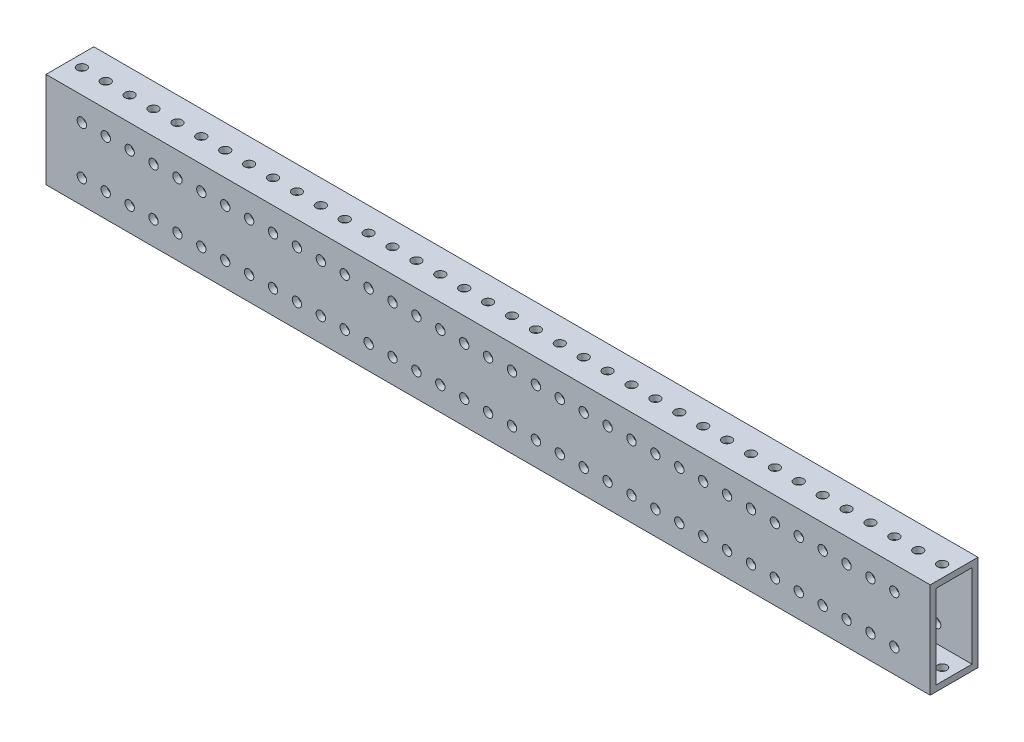
SolidWorks part; units mm, degrees
material "6061-T6 (SS)"
ref_plane "Front Plane" through (0, 0, 0) normal (0, 0, 1) x (1, 0, 0)
ref_plane "Top Plane" through (0, 0, 0) normal (0, 1, 0) x (1, 0, 0)
ref_plane "Right Plane" through (0, 0, 0) normal (1, 0, 0) x (0, 0, -1)
sketch "Sketch1" plane through (0, 0, 0) normal (0, 0, 1) x (1, 0, 0)
  line L1 (0, 0) -> (469.9, 0)
  line L2 (0, 0) -> (0, 50.8)
  line L3 (0, 50.8) -> (469.9, 50.8)
  line L4 (469.9, 0) -> (469.9, 50.8)
  dimension "D1" = 50.8
  dimension "D2" = 469.9
extrude "Boss-Extrude1" add sketch "Sketch1" along normal blind 25.4
shell "Shell1" thickness 3.175 removed face at (469.9, 25.4, 12.7) removed face at (0, 25.4, 12.7)
sketch "Sketch2" plane through (0, 0, 0) normal (0, 0, -1) x (-1, 0, 0)
  line L0 (-469.9, 50.8) -> (0, 50.8) construction
  line L1 (-469.9, 0) -> (-469.9, 50.8) construction
  circle A0 centre (-450.85, 38.1) radius 2.4892
  circle A1 centre (-438.15, 38.1) radius 2.4892
  circle A2 centre (-425.45, 38.1) radius 2.4892
  circle A3 centre (-412.75, 38.1) radius 2.4892
  circle A4 centre (-400.05, 38.1) radius 2.4892
  circle A5 centre (-387.35, 38.1) radius 2.4892
  circle A6 centre (-374.65, 38.1) radius 2.4892
  circle A7 centre (-361.95, 38.1) radius 2.4892
  circle A8 centre (-349.25, 38.1) radius 2.4892
  circle A9 centre (-336.55, 38.1) radius 2.4892
  circle A10 centre (-323.85, 38.1) radius 2.4892
  circle A11 centre (-311.15, 38.1) radius 2.4892
  circle A12 centre (-298.45, 38.1) radius 2.4892
  circle A13 centre (-285.75, 38.1) radius 2.4892
  circle A14 centre (-273.05, 38.1) radius 2.4892
  circle A15 centre (-260.35, 38.1) radius 2.4892
  circle A16 centre (-247.65, 38.1) radius 2.4892
  circle A17 centre (-234.95, 38.1) radius 2.4892
  circle A18 centre (-222.25, 38.1) radius 2.4892
  circle A19 centre (-209.55, 38.1) radius 2.4892
  circle A20 centre (-196.85, 38.1) radius 2.4892
  circle A21 centre (-184.15, 38.1) radius 2.4892
  circle A22 centre (-171.45, 38.1) radius 2.4892
  circle A23 centre (-158.75, 38.1) radius 2.4892
  circle A24 centre (-146.05, 38.1) radius 2.4892
  circle A25 centre (-133.35, 38.1) radius 2.4892
  circle A26 centre (-120.65, 38.1) radius 2.4892
  circle A27 centre (-107.95, 38.1) radius 2.4892
  circle A28 centre (-95.25, 38.1) radius 2.4892
  circle A29 centre (-82.55, 38.1) radius 2.4892
  circle A30 centre (-69.85, 38.1) radius 2.4892
  circle A31 centre (-57.15, 38.1) radius 2.4892
  circle A32 centre (-44.45, 38.1) radius 2.4892
  circle A33 centre (-31.75, 38.1) radius 2.4892
  circle A34 centre (-19.05, 38.1) radius 2.4892
  circle A35 centre (-6.35, 38.1) radius 2.4892 construction
  circle A36 centre (6.35, 38.1) radius 2.4892 construction
  circle A37 centre (19.05, 38.1) radius 2.4892 construction
  circle A38 centre (31.75, 38.1) radius 2.4892 construction
  circle A39 centre (44.45, 38.1) radius 2.4892 construction
  circle A40 centre (-438.15, 12.7) radius 2.4892
  circle A41 centre (-425.45, 12.7) radius 2.4892
  circle A42 centre (-412.75, 12.7) radius 2.4892
  circle A43 centre (-400.05, 12.7) radius 2.4892
  circle A44 centre (-387.35, 12.7) radius 2.4892
  circle A45 centre (-374.65, 12.7) radius 2.4892
  circle A46 centre (-361.95, 12.7) radius 2.4892
  circle A47 centre (-349.25, 12.7) radius 2.4892
  circle A48 centre (-336.55, 12.7) radius 2.4892
  circle A49 centre (-323.85, 12.7) radius 2.4892
  circle A50 centre (-311.15, 12.7) radius 2.4892
  circle A51 centre (-298.45, 12.7) radius 2.4892
  circle A52 centre (-285.75, 12.7) radius 2.4892
  circle A53 centre (-273.05, 12.7) radius 2.4892
  circle A54 centre (-260.35, 12.7) radius 2.4892
  circle A55 centre (-247.65, 12.7) radius 2.4892
  circle A56 centre (-234.95, 12.7) radius 2.4892
  circle A57 centre (-222.25, 12.7) radius 2.4892
  circle A58 centre (-209.55, 12.7) radius 2.4892
  circle A59 centre (-196.85, 12.7) radius 2.4892
  circle A60 centre (-184.15, 12.7) radius 2.4892
  circle A61 centre (-171.45, 12.7) radius 2.4892
  circle A62 centre (-158.75, 12.7) radius 2.4892
  circle A63 centre (-146.05, 12.7) radius 2.4892
  circle A64 centre (-133.35, 12.7) radius 2.4892
  circle A65 centre (-120.65, 12.7) radius 2.4892
  circle A66 centre (-107.95, 12.7) radius 2.4892
  circle A67 centre (-95.25, 12.7) radius 2.4892
  circle A68 centre (-82.55, 12.7) radius 2.4892
  circle A69 centre (-69.85, 12.7) radius 2.4892
  circle A70 centre (-57.15, 12.7) radius 2.4892
  circle A71 centre (-44.45, 12.7) radius 2.4892
  circle A72 centre (-31.75, 12.7) radius 2.4892
  circle A73 centre (-19.05, 12.7) radius 2.4892
  circle A74 centre (-6.35, 12.7) radius 2.4892 construction
  circle A75 centre (6.35, 12.7) radius 2.4892 construction
  circle A76 centre (19.05, 12.7) radius 2.4892 construction
  circle A77 centre (31.75, 12.7) radius 2.4892 construction
  circle A78 centre (44.45, 12.7) radius 2.4892 construction
  circle A79 centre (-450.85, 12.7) radius 2.4892
  dimension "D1" = 4.9784
  dimension "D3" = 19.05
  dimension "D2" = 12.7
  dimension "D6" = 25.4
  dimension "D7" = 12.7
  dimension "D4" = 40
  dimension "D5" = 2
extrude "Cut-Extrude1" cut sketch "Sketch2" against normal blind 25.4
sketch "Sketch3" plane through (0, 50.8, 0) normal (0, 1, 0) x (1, 0, 0)
  line L0 (0, -25.4) -> (0, 0) construction
  line L1 (469.9, 0) -> (0, 0) construction
  line L2 (469.9, -25.4) -> (469.9, 0) construction
  circle A0 centre (6.35, -12.7) radius 2.4892
  circle A1 centre (19.05, -12.7) radius 2.4892
  circle A2 centre (31.75, -12.7) radius 2.4892
  circle A3 centre (44.45, -12.7) radius 2.4892
  circle A4 centre (57.15, -12.7) radius 2.4892
  circle A5 centre (69.85, -12.7) radius 2.4892
  circle A6 centre (82.55, -12.7) radius 2.4892
  circle A7 centre (95.25, -12.7) radius 2.4892
  circle A8 centre (107.95, -12.7) radius 2.4892
  circle A9 centre (120.65, -12.7) radius 2.4892
  circle A10 centre (133.35, -12.7) radius 2.4892
  circle A11 centre (146.05, -12.7) radius 2.4892
  circle A12 centre (158.75, -12.7) radius 2.4892
  circle A13 centre (171.45, -12.7) radius 2.4892
  circle A14 centre (184.15, -12.7) radius 2.4892
  circle A15 centre (196.85, -12.7) radius 2.4892
  circle A16 centre (209.55, -12.7) radius 2.4892
  circle A17 centre (222.25, -12.7) radius 2.4892
  circle A18 centre (234.95, -12.7) radius 2.4892
  circle A19 centre (247.65, -12.7) radius 2.4892
  circle A20 centre (260.35, -12.7) radius 2.4892
  circle A21 centre (273.05, -12.7) radius 2.4892
  circle A22 centre (285.75, -12.7) radius 2.4892
  circle A23 centre (298.45, -12.7) radius 2.4892
  circle A24 centre (311.15, -12.7) radius 2.4892
  circle A25 centre (323.85, -12.7) radius 2.4892
  circle A26 centre (336.55, -12.7) radius 2.4892
  circle A27 centre (349.25, -12.7) radius 2.4892
  circle A28 centre (361.95, -12.7) radius 2.4892
  circle A29 centre (374.65, -12.7) radius 2.4892
  circle A30 centre (387.35, -12.7) radius 2.4892
  circle A31 centre (400.05, -12.7) radius 2.4892
  circle A32 centre (412.75, -12.7) radius 2.4892
  circle A33 centre (425.45, -12.7) radius 2.4892
  circle A34 centre (438.15, -12.7) radius 2.4892
  circle A35 centre (450.85, -12.7) radius 2.4892
  circle A36 centre (463.55, -12.7) radius 2.4892
  circle A37 centre (476.25, -12.7) radius 2.4892 construction
  circle A38 centre (488.95, -12.7) radius 2.4892 construction
  circle A39 centre (501.65, -12.7) radius 2.4892 construction
  circle A40 centre (463.55, -12.7) radius 2.4892
  dimension "D1" = 4.9784
  dimension "D2" = 6.35
  dimension "D3" = 12.7
  dimension "D5" = 12.7
  dimension "D6" = 6.35
  dimension "D4" = 40
extrude "Cut-Extrude2" cut sketch "Sketch3" against normal blind 50.8 contours A0 | A1 | A2 | A3 | A4 | A5 | A6 | A7 | A8 | A9 | A10 | A11 | A12 | A13 | A14 | A15 | A16 | A17 | A18 | A19 | A20 | A21 | A22 | A23 | A24 | A25 | A26 | A27 | A28 | A29 | A30 | A31 | A32 | A33 | A34 | A35 | A36 region at (6.35, 50.8, 12.7) region at (19.05, 50.8, 12.7) region at (31.75, 50.8, 12.7) region at (44.45, 50.8, 12.7) region at (57.15, 50.8, 12.7) region at (69.85, 50.8, 12.7) region at (82.55, 50.8, 12.7) region at (95.25, 50.8, 12.7) region at (107.95, 50.8, 12.7) region at (120.65, 50.8, 12.7) region at (133.35, 50.8, 12.7) region at (146.05, 50.8, 12.7) region at (158.75, 50.8, 12.7) region at (171.45, 50.8, 12.7) region at (184.15, 50.8, 12.7) region at (196.85, 50.8, 12.7) region at (209.55, 50.8, 12.7) region at (222.25, 50.8, 12.7) region at (234.95, 50.8, 12.7) region at (247.65, 50.8, 12.7) region at (260.35, 50.8, 12.7) region at (273.05, 50.8, 12.7) region at (285.75, 50.8, 12.7) region at (298.45, 50.8, 12.7) region at (311.15, 50.8, 12.7) region at (323.85, 50.8, 12.7) region at (336.55, 50.8, 12.7) region at (349.25, 50.8, 12.7) region at (361.95, 50.8, 12.7) region at (374.65, 50.8, 12.7) region at (387.35, 50.8, 12.7) region at (400.05, 50.8, 12.7) region at (412.75, 50.8, 12.7) region at (425.45, 50.8, 12.7) region at (438.15, 50.8, 12.7) region at (450.85, 50.8, 12.7) region at (463.55, 50.8, 12.7)
